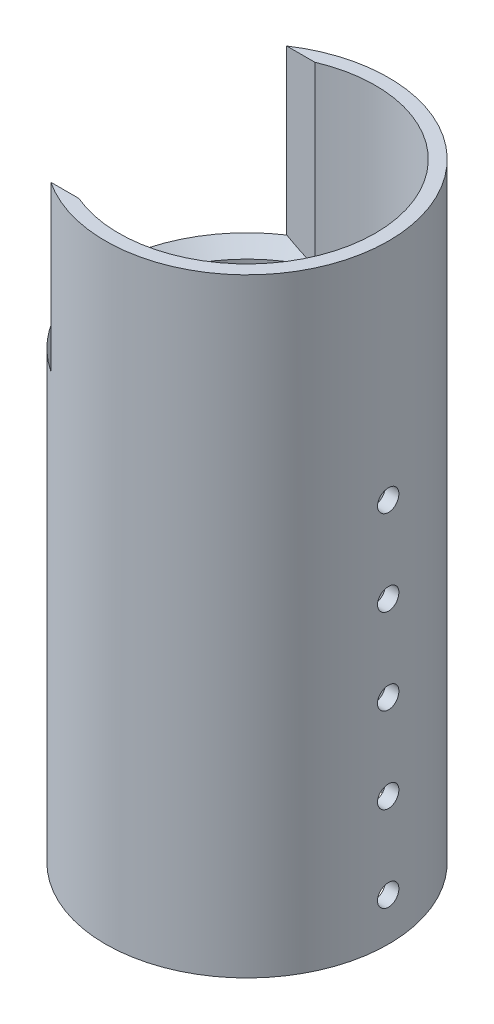
SolidWorks part; units mm, degrees
ref_plane "Front Plane" through (0, 0, 0) normal (0, 0, 1) x (1, 0, 0)
ref_plane "Top Plane" through (0, 0, 0) normal (0, 1, 0) x (1, 0, 0)
ref_plane "Right Plane" through (0, 0, 0) normal (1, 0, 0) x (0, 0, -1)
sketch "Sketch1" plane through (0, 0, 0) normal (0, 1, 0) x (1, 0, 0)
  line L0 (-221.1713, 0) -> (221.1713, 0) construction
  line L1 (0, -168.4638) -> (0, 168.4638) construction
  circle A0 centre (0, 0) radius 76.2
  circle A1 centre (0, 0) radius 84.1375
  point P4 (0, 0)
  point P8 (0, 0)
  dimension "D1" = 152.4
  dimension "D2" = 168.275
extrude "Boss-Extrude1" add sketch "Sketch1" along normal mid plane 361.95
sketch "Sketch2" plane through (0, 180.975, 0) normal (0, 1, 0) x (1, 0, 0)
  line L0 (-170.9161, 0) -> (170.9161, 0) construction
  line L1 (0, -130.7841) -> (0, 130.7841) construction
  line L2 (0, 0) -> (-42.1237, 63.4983)
  line L3 (0, 0) -> (-42.1186, -63.5017)
  line L4 (57.8521, -87.2229) -> (-57.8521, 87.2229) construction
  line L5 (-62.231, -93.825) -> (62.231, 93.825) construction
  line L6 (-42.1237, 63.4983) -> (-46.5059, 70.1165)
  line L7 (-42.1186, -63.5017) -> (-46.5059, -70.1165)
  arc A2 (-46.5059, 70.1165) -> (-46.5059, -70.1165) centre (0, 0) ccw
  point P4 (0, 0)
  point P8 (0, 0)
  point P10 (-21.0618, 31.7492)
  point P14 (-38.1, 0)
  point P15 (-21.0593, -31.7508)
  point P18 (0, 0)
  point P22 (0, 0)
  dimension "D5" = 112.885
  dimension "D1" = 63.5
  dimension "D2" = 38.1
  dimension "D3" = 38.1
  dimension "D6" = 33.555
  dimension "D7" = 33.555
extrude "Cut-Extrude1" cut sketch "Sketch2" against normal blind 95.25
sketch "Sketch3" plane through (0, 180.975, 0) normal (0, 1, 0) x (1, 0, 0)
  line L0 (-192.0709, 0) -> (192.0709, 0) construction
  line L1 (0, -133.6334) -> (0, 133.6334) construction
  line L3 (-46.5059, -70.1165) -> (-29.8349, -70.1165)
  line L5 (-46.5059, -70.1165) -> (-42.1186, -63.5017)
  line L6 (-46.5059, 70.1165) -> (-29.8349, 70.1165)
  line L7 (-46.5059, 70.1165) -> (-42.1237, 63.4983)
  arc A0 (-42.1186, -63.5017) -> (-42.1237, 63.4983) centre (0, 0) ccw construction
  arc A2 (-29.8349, -70.1165) -> (-42.1186, -63.5017) centre (0, 0) cw
  arc A3 (-29.8349, 70.1165) -> (-42.1237, 63.4983) centre (0, 0) ccw
  point P4 (0, 0)
  point P8 (0, 0)
extrude "Cut-Extrude2" cut sketch "Sketch3" against normal blind 95.25
chamfer "Chamfer2" distance 10 angle 45 1 edges at (-76.2, 85.725, 0)
sketch "Sketch7" plane through (0, 0, 0) normal (1, 0, 0) x (0, 0, -1)
  line L0 (-225.4525, 0) -> (225.4525, 0) construction
  line L1 (0, -308.5357) -> (0, 308.5357) construction
  line L2 (-165.2803, 47.625) -> (165.2803, 47.625) construction
  line L3 (-142.3887, -3.175) -> (142.3887, -3.175) construction
  line L4 (84.1375, 180.975) -> (-84.1375, 180.975) construction
  circle A1 centre (0, 47.625) radius 6.35
  circle A2 centre (0, -3.175) radius 6.35
  circle A3 centre (0, -53.975) radius 6.35
  circle A4 centre (0, -104.775) radius 6.35
  circle A5 centre (0, -155.575) radius 6.35
  point P4 (0, 0)
  point P8 (0, 0)
  point P13 (0, 47.625)
  point P16 (0, -3.175)
  dimension "D3" = 12.7
  dimension "D4" = 12.7
  dimension "D1" = 133.35
  dimension "D2" = 50.8
  dimension "D5" = 4
extrude "Cut-Extrude9" cut sketch "Sketch7" along normal blind 95.25
